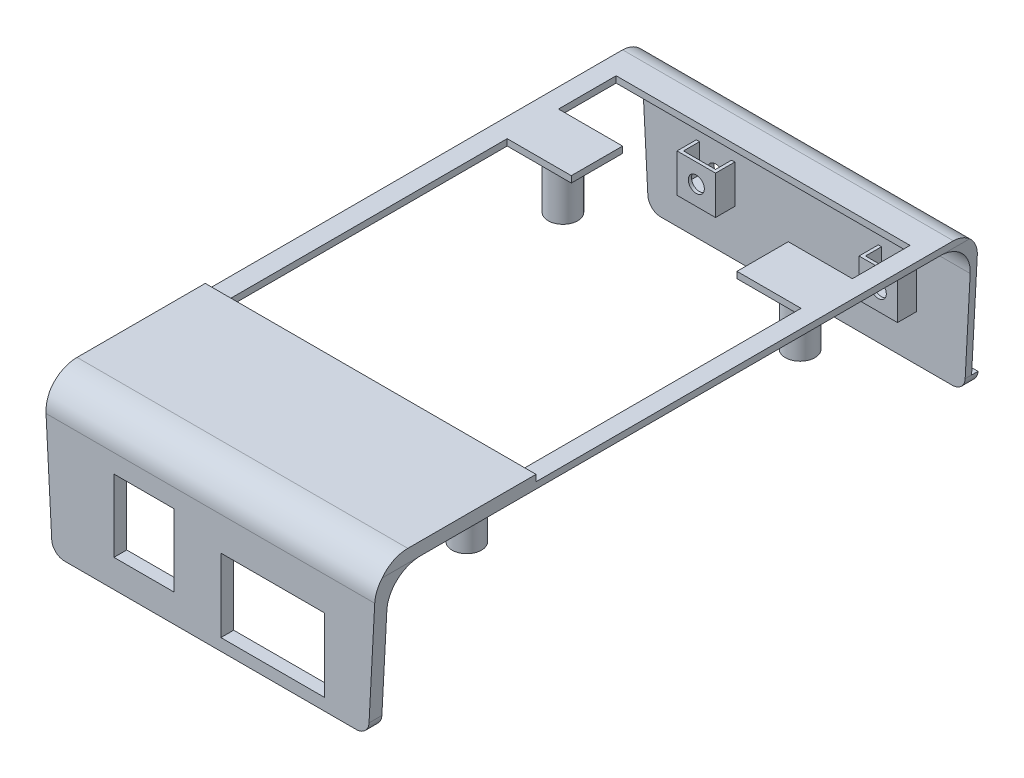
SolidWorks part; units mm, degrees
ref_plane "Front Plane" through (0, 0, 0) normal (0, 0, 1) x (1, 0, 0)
ref_plane "Top Plane" through (0, 0, 0) normal (0, 1, 0) x (1, 0, 0)
ref_plane "Right Plane" through (0, 0, 0) normal (1, 0, 0) x (0, 0, -1)
sketch "Sketch1" plane through (0, 0, 0) normal (1, 0, 0) x (0, 0, -1)
  line L0 (-45.5, 0) -> (-45.5, 21.5)
  line L1 (-45.5, 21.5) -> (45.5, 21.5)
  line L2 (45.5, 21.5) -> (45.5, 0)
  line L3 (45.5, 0) -> (47.5, 0)
  line L4 (47.5, 0) -> (47.5, 23.5)
  line L5 (47.5, 23.5) -> (-47.5, 23.5)
  line L6 (-47.5, 23.5) -> (-47.5, 0)
  line L7 (-47.5, 0) -> (-45.5, 0)
  line L8 (0, 0) -> (26.8181, 0) construction
  line L9 (0, 62.6457) -> (0, -19.6457) construction
  point P13 (0, 21.5)
  dimension "D1" = 2
  dimension "D2" = 2
  dimension "D3" = 23.5
  dimension "D4" = 2
  dimension "D5" = 95
extrude "Boss-Extrude1" add sketch "Sketch1" along normal blind 25.8 and the other way blind 25.8
sketch "Sketch3" plane through (0, 0, -47.5) normal (0, 0, -1) x (-1, 0, 0)
  line L0 (-25.8, 21.5) -> (-24.65, 0)
  line L1 (-25.8, 0) -> (-25.8, 23.5) construction
  line L2 (25.8, 0) -> (-25.8, 0) construction
  line L3 (-24.65, 0) -> (-25.8, 0)
  line L4 (-25.8, 0) -> (-25.8, 21.5)
  line L5 (25.8, 21.5) -> (24.65, 0)
  line L6 (25.8, 0) -> (25.8, 23.5) construction
  line L7 (24.65, 0) -> (25.8, 0)
  line L8 (25.8, 0) -> (25.8, 21.5)
  dimension "D1" = 2
  dimension "D2" = 2
  dimension "D3" = 1.15
  dimension "D4" = 1.15
extrude "Cut-Extrude2" cut sketch "Sketch3" against normal blind 105.5
fillet "Fillet3" radius 2 4 edges at (-24.65, 0, -46.5) (-24.65, 0, 46.5) (24.65, 0, 46.5) (24.65, 0, -46.5)
fillet "Fillet2" radius 5 4 edges at (0, 21.5, 45.5) (0, 23.5, 47.5) (0, 23.5, -47.5) (0, 21.5, -45.5)
sketch "Sketch4" plane through (0, 21.5, 0) normal (0, -1, 0) x (1, 0, 0)
  line L0 (84.451, 0) -> (-80.3426, 0) construction
  line L1 (0, -58.5841) -> (0, 64.2897) construction
  line L2 (60.1496, -26) -> (-78.6719, -26) construction
  line L3 (53.4667, -18) -> (-77.4569, -18) construction
  line L4 (53.4667, 18) -> (-77.4569, 18) construction
  line L5 (60.1496, 26) -> (-82.0134, 26) construction
  line L6 (18.5, -56.1539) -> (18.5, 92.9112) construction
  line L7 (17, -56.1539) -> (17, 88.4495) construction
  line L8 (-17, -56.1539) -> (-17, 98.1603) construction
  line L9 (-18.5, -56.1539) -> (-18.5, 103.4094) construction
  circle A0 centre (-18.5, -26) radius 2.3
  circle A1 centre (18.5, -26) radius 2.3
  circle A2 centre (-18.5, 26) radius 2.3
  circle A3 centre (18.5, 26) radius 2.3
  dimension "D9" = 4.6
  dimension "D1" = 26
  dimension "D2" = 26
  dimension "D3" = 18
  dimension "D4" = 18
  dimension "D5" = 17
  dimension "D6" = 17
  dimension "D7" = 18.5
  dimension "D8" = 18.5
extrude "Boss-Extrude2" add sketch "Sketch4" along normal blind 9
sketch "Sketch8" plane through (0, 0, 47.5) normal (0, 0, 1) x (1, 0, 0)
  line L1 (-15.0476, 15.6183) -> (-5.6436, 15.6183)
  line L2 (-15.0476, 15.6183) -> (-15.0476, 4.3583)
  line L3 (-15.0476, 4.3583) -> (-5.6436, 4.3583)
  line L4 (-5.6436, 15.6183) -> (-5.6436, 4.3583)
  line L5 (1.6382, 13.2784) -> (17.7864, 13.2784)
  line L6 (1.6382, 13.2784) -> (1.6382, 1.8631)
  line L7 (1.6382, 1.8631) -> (17.7864, 1.8631)
  line L8 (17.7864, 13.2784) -> (17.7864, 1.8631)
extrude "Cut-Extrude5" cut sketch "Sketch8" against normal blind 10
sketch "Sketch9" plane through (25.8, 0, 0) normal (1, 0, 0) x (0, 0, -1)
  line L0 (-22.5, 23.5) -> (-22.5, 22.4986)
  line L1 (42.5, 23.5) -> (-42.5, 23.5) construction
  line L2 (42.6046, 22.4986) -> (-22.5, 22.4986)
  line L3 (46.5, 18.5) -> (46.5, 1.8932)
  line L4 (46.5, 1.8932) -> (47.5, 1.8932)
  line L5 (47.5, 1.8932) -> (47.5, 18.5) construction
  line L6 (47.5, 1.8932) -> (47.5, 18.5)
  line L7 (-22.5, 23.5) -> (42.5, 23.5)
  line L8 (45.5, 1.8932) -> (47.5, 1.8932) construction
  arc A0 (42.6046, 22.4986) -> (46.5, 18.5) centre (42.5, 18.5) cw
  arc A1 (42.5, 23.5) -> (47.5, 18.5) centre (42.5, 18.5) cw
  arc A2 (46.5, 21.5) -> (42.5, 23.5) centre (42.5, 18.5) ccw construction
  dimension "D4" = 4
  dimension "D1" = 1
  dimension "D2" = 1.0014
  dimension "D3" = 70
extrude "Cut-Extrude6" cut sketch "Sketch9" against normal blind 56
sketch "Sketch10" plane through (0, 22.4986, 0) normal (0, 1, 0) x (1, 0, 0)
  line L0 (-22.8, -22.5) -> (-22.8, 21.6046)
  line L1 (-25.8, -22.5) -> (25.8, -22.5) construction
  line L3 (23.0459, 21.6046) -> (13.0459, 21.6046)
  line L5 (-25.8, 42.6046) -> (25.8, 42.6046) construction
  line L6 (-22.8, 29.6046) -> (-22.8, 38.6046)
  line L7 (-22.8, 38.6046) -> (23.0459, 38.6046)
  line L8 (23.0459, 38.6046) -> (23.0459, 29.6046)
  line L9 (-22.8, -22.5) -> (23.0459, -22.5)
  line L10 (23.0459, 21.6046) -> (23.0459, -22.5)
  line L11 (23.0459, 29.6046) -> (13.0459, 29.6046)
  line L12 (13.0459, 21.6046) -> (13.0459, 29.6046)
  line L13 (-22.8, 21.6046) -> (-12.8, 21.6046)
  line L15 (-22.8, 29.6046) -> (-12.8, 29.6046)
  line L16 (-12.8, 21.6046) -> (-12.8, 29.6046)
  point P12 (18.0459, 29.6046)
  dimension "D3" = 4
  dimension "D4" = 10
  dimension "D5" = 8
  dimension "D6" = 9
  dimension "D7" = 9
  dimension "D8" = 8
  dimension "D9" = 10
extrude "Cut-Extrude7" cut sketch "Sketch10" against normal blind 56
sketch "Sketch11" plane through (0, 0, -46.5) normal (0, 0, -1) x (-1, 0, 0)
  line L0 (25.6395, 18.5) -> (24.7513, 1.8932) construction
  line L3 (-24.7513, 1.8932) -> (-25.6395, 18.5) construction
  line L4 (-17.1954, 7.1966) -> (-11.1954, 7.1966)
  line L5 (-17.1954, 7.1966) -> (-17.1954, 13.1966)
  line L6 (-17.1954, 13.1966) -> (-11.1954, 13.1966)
  line L7 (-11.1954, 7.1966) -> (-11.1954, 13.1966)
  line L8 (-17.1954, 7.1966) -> (-11.1954, 13.1966) construction
  line L9 (-17.1954, 13.1966) -> (-11.1954, 7.1966) construction
  line L10 (11.1954, 7.1966) -> (17.1954, 7.1966)
  line L11 (11.1954, 7.1966) -> (11.1954, 13.1966)
  line L12 (11.1954, 13.1966) -> (17.1954, 13.1966)
  line L13 (17.1954, 7.1966) -> (17.1954, 13.1966)
  line L14 (11.1954, 7.1966) -> (17.1954, 13.1966) construction
  point P0 (14.1954, 10.1966)
  point P3 (25.1954, 10.1966)
  point P4 (-14.1954, 10.1966)
  point P9 (-25.1954, 10.1966)
  dimension "D4" = 6
  dimension "D1" = 11
  dimension "D2" = 11
  dimension "D5" = 6
  dimension "D6" = 6
  dimension "D7" = 6
extrude "Boss-Extrude3" add sketch "Sketch11" against normal blind 4
sketch "Sketch12" plane through (0, 0, -46.5) normal (0, 0, -1) x (-1, 0, 0)
  line L0 (25.1954, 10.1966) -> (-25.1954, 10.1966) construction
  line L1 (25.6395, 18.5) -> (24.7513, 1.8932) construction
  line L2 (-24.7513, 1.8932) -> (-25.6395, 18.5) construction
  circle A0 centre (14.1954, 10.1966) radius 1.25
  circle A1 centre (-14.1954, 10.1966) radius 1.25
  dimension "D1" = 2.5
  dimension "D2" = 11
  dimension "D3" = 11
extrude "Cut-Extrude8" cut sketch "Sketch12" against normal blind 7
sketch "Sketch13" plane through (0, 13.1966, 0) normal (0, 1, 0) x (1, 0, 0)
  line L0 (17.1954, 45.5) -> (11.1954, 45.5) construction
  line L1 (11.6954, 45.5) -> (16.6954, 45.5)
  line L2 (11.6954, 45.5) -> (11.6954, 43)
  line L3 (11.6954, 43) -> (16.6954, 43)
  line L4 (16.6954, 45.5) -> (16.6954, 43)
  line L5 (11.1954, 42.5) -> (11.1954, 45.5) construction
  line L7 (11.1954, 42.5) -> (17.1954, 42.5) construction
  line L8 (17.1954, 42.5) -> (17.1954, 45.5) construction
  line L9 (-11.1954, 45.5) -> (-17.1954, 45.5) construction
  line L10 (-16.6954, 45.5) -> (-11.6954, 45.5)
  line L11 (-16.6954, 45.5) -> (-16.6954, 43)
  line L12 (-16.6954, 43) -> (-11.6954, 43)
  line L13 (-11.6954, 45.5) -> (-11.6954, 43)
  line L14 (-17.1954, 42.5) -> (-17.1954, 45.5) construction
  line L15 (-17.1954, 42.5) -> (-11.1954, 42.5) construction
  line L16 (-11.1954, 42.5) -> (-11.1954, 45.5) construction
  point P10 (16.6954, 44.25)
  point P21 (-17.1954, 44)
  point P24 (-14.1954, 42.5)
  point P27 (-11.1954, 44)
  dimension "D1" = 0.5
  dimension "D2" = 0.5
  dimension "D3" = 0.5
  dimension "D4" = 0.5
  dimension "D5" = 0.5
  dimension "D6" = 0.5
extrude "Cut-Extrude9" cut sketch "Sketch13" against normal blind 4.5
